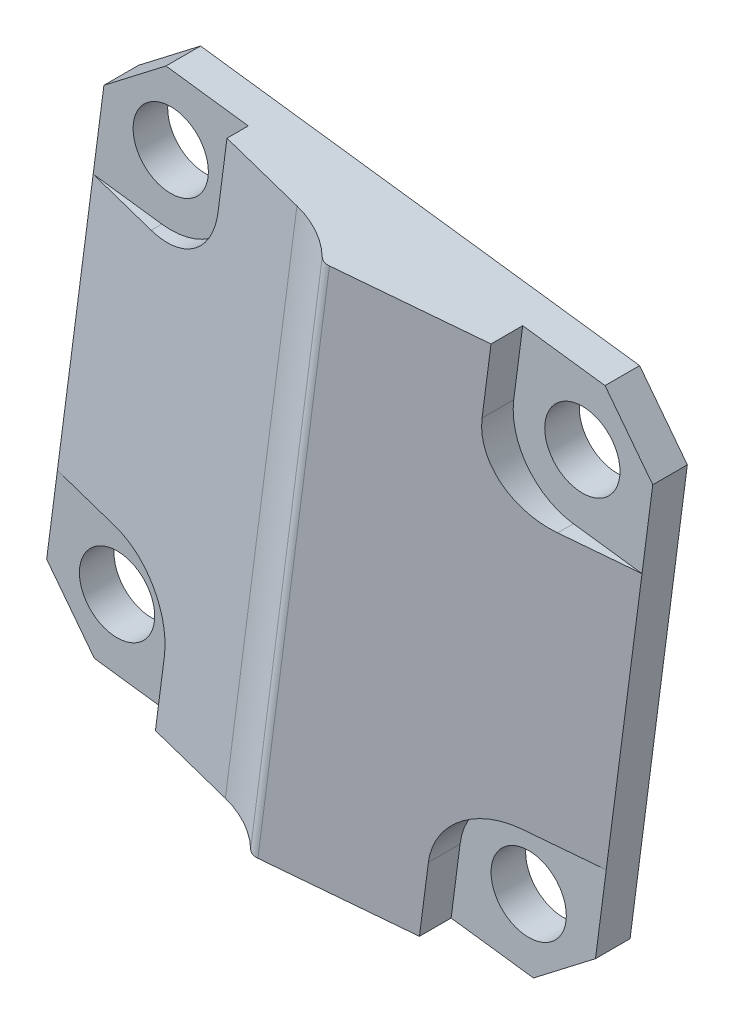
SolidWorks part; units mm, degrees
material "PET"
ref_plane "Front Plane" through (0, 0, 0) normal (0, 0, 1) x (1, 0, 0)
ref_plane "Top Plane" through (0, 0, 0) normal (0, 1, 0) x (1, 0, 0)
ref_plane "Right Plane" through (0, 0, 0) normal (1, 0, 0) x (0, 0, -1)
sketch "Reference" plane through (0, 0, 0) normal (0, 0, 1) x (1, 0, 0)
  line L2 (37.0142, -65.193) -> (37.0142, -133.528)
  line L3 (-111.7057, -139.0338) -> (-111.7057, -78.8372)
  line L4 (9.0014, -65.8409) -> (-3.9179, -104.9724)
  line L6 (-23.1411, -100.3781) -> (-17.3713, -56.1343)
  line L9 (-36.2613, -53.6709) -> (1.5188, -58.5978)
  arc A4 (37.0142, -133.528) -> (-111.7057, -139.0338) centre (-35.2286, -193.468) ccw
  point P13 (8.0286, -68.7874)
  dimension "D1" = 93.8714
  dimension "D2" = 3.103
  dimension "D3" = 1.5188
  dimension "D4" = 8.0286
  dimension "D5" = 37.0142
  dimension "D6" = 3.9179
  dimension "D7" = 17.3713
  dimension "D8" = 23.1411
  dimension "D9" = 35.2286
  dimension "D10" = 53.6709
  dimension "D11" = 111.7057
  dimension "D14" = 65.193
  dimension "D15" = 78.8372
sketch "Sketch2" plane through (0, 0, 0) normal (0, 0, 1) x (1, 0, 0)
  line L0 (-37.3768, -111.3292) -> (-34.0922, -86.1425)
  line L1 (-37.3768, -111.3292) -> (-12.19, -114.6138)
  line L2 (-34.0922, -86.1425) -> (-8.9054, -89.4271)
  line L3 (-12.19, -114.6138) -> (-8.9054, -89.4271)
  line L4 (-37.3768, -111.3292) -> (-8.9054, -89.4271) construction
  line L5 (-34.0922, -86.1425) -> (-12.19, -114.6138) construction
  line L6 (-23.1411, -100.3781) -> (-17.3713, -56.1343) construction
  point P1 (-23.1411, -100.3781)
  dimension "D1" = 25.4
  dimension "D2" = 25.4
extrude "Boss-Extrude1" add sketch "Sketch2" along normal blind 1.5875
sketch "Sketch3" plane through (-11.6161, -89.0736, 0) normal (0.1293, 0.9916, 0) x (0.9916, -0.1293, 0)
  line L0 (2.7336, -1.5875) -> (-22.6664, -1.5875) construction
  line L1 (2.7336, 0) -> (-22.6664, 0) construction
  line L2 (-11.5539, -4.5085) -> (-8.3789, -4.5085)
  line L3 (-9.9664, -4.5085) -> (-9.9664, 0) construction
  line L4 (-14.4749, -1.5875) -> (-5.4579, -1.5875)
  arc A0 (-14.4749, -1.5875) -> (-11.5539, -4.5085) centre (-14.4749, -4.5085) cw
  arc A1 (-5.4579, -1.5875) -> (-8.3789, -4.5085) centre (-5.4579, -4.5085) ccw
  point P16 (-9.9664, -1.5875)
  dimension "D1" = 4.5085
  dimension "D2" = 1.5875
extrude "Boss-Extrude2" [suppressed] add sketch "Sketch3" against normal up to surface (12.7 mm away) up to face at (-24.7834, -112.9715, 0.7937)
sketch "Sketch4" plane through (-11.6161, -89.0736, 0) normal (0.1293, 0.9916, 0) x (0.9916, -0.1293, 0)
  line L0 (-22.6664, -1.5875) -> (-12.4842, -3.1552)
  line L1 (-9.9664, -4.4958) -> (2.7336, -1.5875)
  line L2 (2.7336, -1.5875) -> (-22.6664, -1.5875)
  line L3 (-13.1414, -7.424) -> (-12.4842, -3.1552) construction
  line L4 (-13.1414, -7.424) -> (-13.1414, 0) construction
  line L5 (2.7336, 0) -> (-22.6664, 0) construction
  arc A0 (-12.4842, -3.1552) -> (-9.9664, -4.4958) centre (-13.1414, -7.424) cw
  dimension "D1" = 4.4958
  dimension "D2" = 3.175
  dimension "D3" = 1.3406
extrude "Boss-Extrude3" add sketch "Sketch4" against normal up to surface (25.4 mm away) up to face at (-24.7834, -112.9715, 0.7937)
fillet "Fillet2" radius 0.508 1 edges at (-23.1411, -100.3781, 4.4958)
hole_wizard "#4 Clearance Hole1" positions "Sketch7" profile "Sketch8" hole size "#4" standard "ANSI Inch" end condition through all
sketch "Sketch7" plane through (0, 0, 0) normal (0, 0, -1) x (-1, 0, 0)
  line L0 (12.19, -114.6138) -> (8.9054, -89.4271) construction
  line L1 (8.9054, -89.4271) -> (34.0922, -86.1425) construction
  line L2 (9.316, -92.5754) -> (34.5027, -89.2908) construction
  line L4 (34.0922, -86.1425) -> (37.3768, -111.3292) construction
  line L6 (30.9438, -86.553) -> (34.2284, -111.7398) construction
  line L7 (37.3768, -111.3292) -> (12.19, -114.6138) construction
  line L9 (36.9662, -108.1808) -> (11.7795, -111.4654) construction
  line L11 (12.0538, -89.0165) -> (15.3384, -114.2032) construction
  point P0 (12.4643, -92.1648)
  point P2 (31.3544, -89.7014)
  point P4 (33.8178, -108.5914)
  point P6 (14.9278, -111.0549)
  dimension "D1" = 3.175
  dimension "D2" = 3.175
  dimension "D3" = 3.175
  dimension "D4" = 3.175
sketch "Sketch8" plane through (-12.4643, -92.1648, 0) normal (1, 0, 0) x (0, 1, 0)
  line L0 (0, 0) -> (0, 4.4453)
  line L1 (0, 4.4453) -> (1.7272, 4.4453)
  line L2 (1.7272, 4.4453) -> (1.7272, 0)
  line L5 (1.7272, 0) -> (0, 0)
  line L11 (0, -6.35) -> (0, 107.95) construction
  dimension "Thru Hole Dia." = 3.4544
  dimension "Thru Hole Depth" = 4.4453
sketch "Sketch9" plane through (0, 0, 0) normal (0, 0, -1) x (-1, 0, 0)
  line L0 (33.4073, -105.4431) -> (39.9741, -104.5867)
  line L1 (39.9741, -104.5867) -> (39.9741, -116.0838)
  line L3 (34.0922, -86.1425) -> (37.3768, -111.3292) construction
  line L4 (27.28, -112.6459) -> (37.3768, -111.3292) construction
  line L5 (30.6695, -109.002) -> (31.7125, -117.0002)
  line L6 (31.7125, -117.0002) -> (39.9741, -116.0838)
  line L7 (35.7345, -98.7358) -> (10.5477, -102.0204) construction
  line L8 (12.19, -114.6138) -> (8.9054, -89.4271) construction
  line L9 (21.4988, -87.7848) -> (24.7834, -112.9715) construction
  line L10 (8.9054, -89.4271) -> (34.0922, -86.1425) construction
  line L11 (37.3768, -111.3292) -> (12.19, -114.6138) construction
  line L12 (27.163, -82.1138) -> (35.3833, -80.8808)
  line L13 (28.2061, -90.1119) -> (27.163, -82.1138)
  line L14 (38.3318, -91.9933) -> (35.3833, -80.8808)
  line L15 (31.765, -92.8497) -> (38.3318, -91.9933)
  line L16 (12.8749, -95.3132) -> (6.3081, -96.1695)
  line L17 (6.3081, -96.1695) -> (6.3081, -84.6725)
  line L18 (15.6127, -91.7542) -> (14.5696, -83.7561)
  line L19 (14.5696, -83.7561) -> (6.3081, -84.6725)
  line L20 (19.1192, -118.6425) -> (10.8989, -119.8755)
  line L21 (18.0761, -110.6443) -> (19.1192, -118.6425)
  line L22 (7.9504, -108.7629) -> (10.8989, -119.8755)
  line L23 (14.5172, -107.9065) -> (7.9504, -108.7629)
  arc A0 (33.4073, -105.4431) -> (30.6695, -109.002) centre (33.8178, -108.5914) ccw
  arc A4 (31.765, -92.8497) -> (28.2061, -90.1119) centre (31.3544, -89.7014) cw
  arc A5 (12.8749, -95.3132) -> (15.6127, -91.7542) centre (12.4643, -92.1648) ccw
  arc A6 (14.5172, -107.9065) -> (18.0761, -110.6443) centre (14.9278, -111.0549) cw
extrude "Cut-Extrude3" cut sketch "Sketch9" along normal offset from surface (4.7625 mm away) 1.5875 from offset 6.35 up to face at (-14.1915, -92.1648, 0) offset against normal yes
chamfer "Chamfer1" distance 2.54 angle 45 4 edges at (-8.9054, -89.4271, 0.7937) (-12.19, -114.6138, 0.7937) (-37.3768, -111.3292, 0.7937) (-34.0922, -86.1425, 0.7937)
